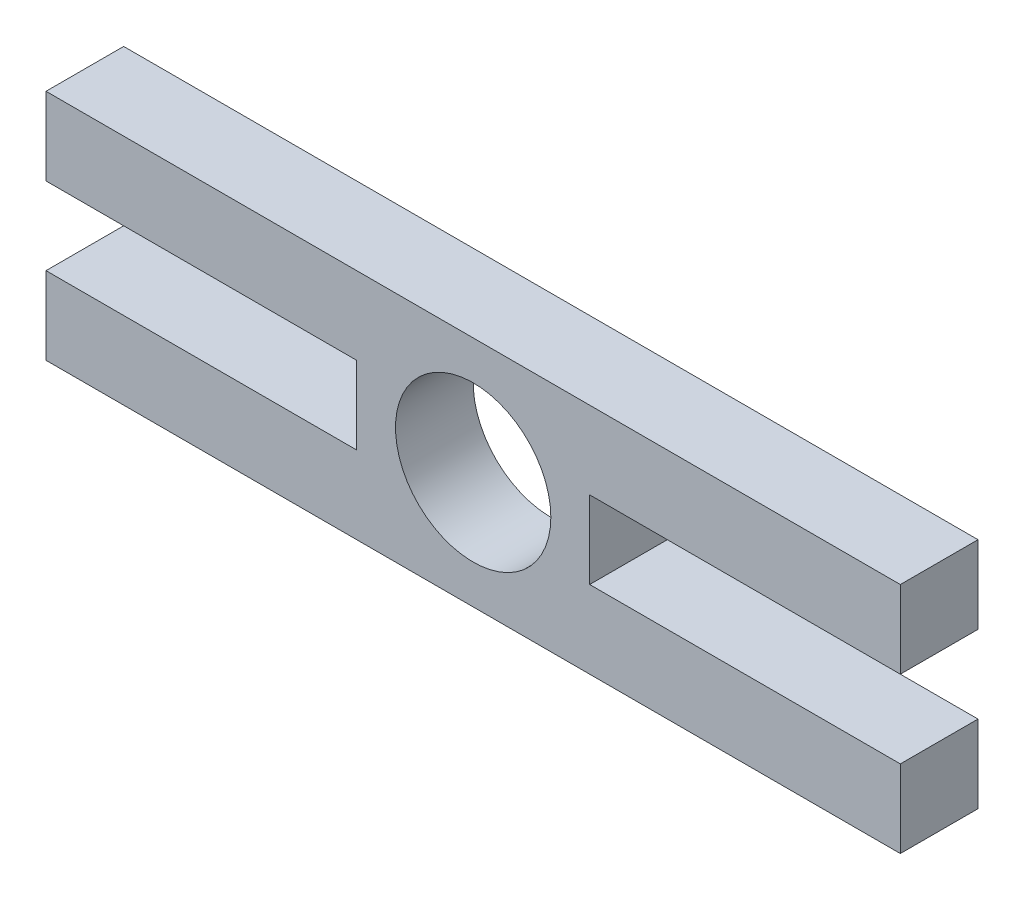
SolidWorks part; units mm, degrees
ref_plane "Front Plane" through (0, 0, 0) normal (0, 0, 1) x (1, 0, 0)
ref_plane "Top Plane" through (0, 0, 0) normal (0, 1, 0) x (1, 0, 0)
ref_plane "Right Plane" through (0, 0, 0) normal (1, 0, 0) x (0, 0, -1)
sketch "Sketch1" plane through (0, 0, 0) normal (0, 0, 1) x (1, 0, 0)
  line L1 (-50.8, 0) -> (-50.8, 6.35)
  line L2 (-50.8, 6.35) -> (0, 6.35)
  line L3 (0, 6.35) -> (0, 19.05)
  line L4 (0, 19.05) -> (-50.8, 19.05)
  line L5 (-50.8, 19.05) -> (-50.8, 25.4)
  line L7 (-50.8, 19.05) -> (-97.7976, 19.05) construction
  line L8 (-97.7976, 19.05) -> (-97.7976, 6.35) construction
  line L9 (-97.7976, 6.35) -> (-50.8, 6.35) construction
  line L10 (0, 12.7) -> (6.35, 12.7) construction
  line L11 (6.35, 12.7) -> (6.35, 4.7841) construction
  line L12 (31.75, 12.7) -> (31.75, 4.7841) construction
  line L13 (19.05, 25.4) -> (19.05, -5.9402) construction
  line L14 (88.9, 0) -> (88.9, 6.35)
  line L15 (88.9, 19.05) -> (88.9, 25.4)
  line L16 (38.1, 12.7) -> (31.75, 12.7) construction
  line L18 (38.1, 19.05) -> (88.9, 19.05)
  line L19 (38.1, 6.35) -> (38.1, 19.05)
  line L20 (88.9, 6.35) -> (38.1, 6.35)
  line L22 (19.05, 31.75) -> (-50.8, 31.75)
  line L23 (-50.8, 31.75) -> (-50.8, 25.4)
  line L24 (19.05, 31.75) -> (88.9, 31.75)
  line L25 (88.9, 31.75) -> (88.9, 25.4)
  line L26 (88.9, -6.35) -> (88.9, 0)
  line L27 (19.05, -6.35) -> (88.9, -6.35)
  line L28 (-50.8, -6.35) -> (-50.8, 0)
  line L29 (19.05, -6.35) -> (-50.8, -6.35)
  circle A0 centre (19.05, 12.7) radius 12.7
  circle A3 centre (19.05, 12.7) radius 19.05 construction
  dimension "D1" = 25.4
  dimension "D6" = 38.1
  dimension "D2" = 6.35
  dimension "D3" = 12.7
  dimension "D4" = 6.35
  dimension "D5" = 50.8
  dimension "D7" = 12.7
  dimension "D8" = 69.85
extrude "Boss-Extrude1" add sketch "Sketch1" along normal blind 12.7
